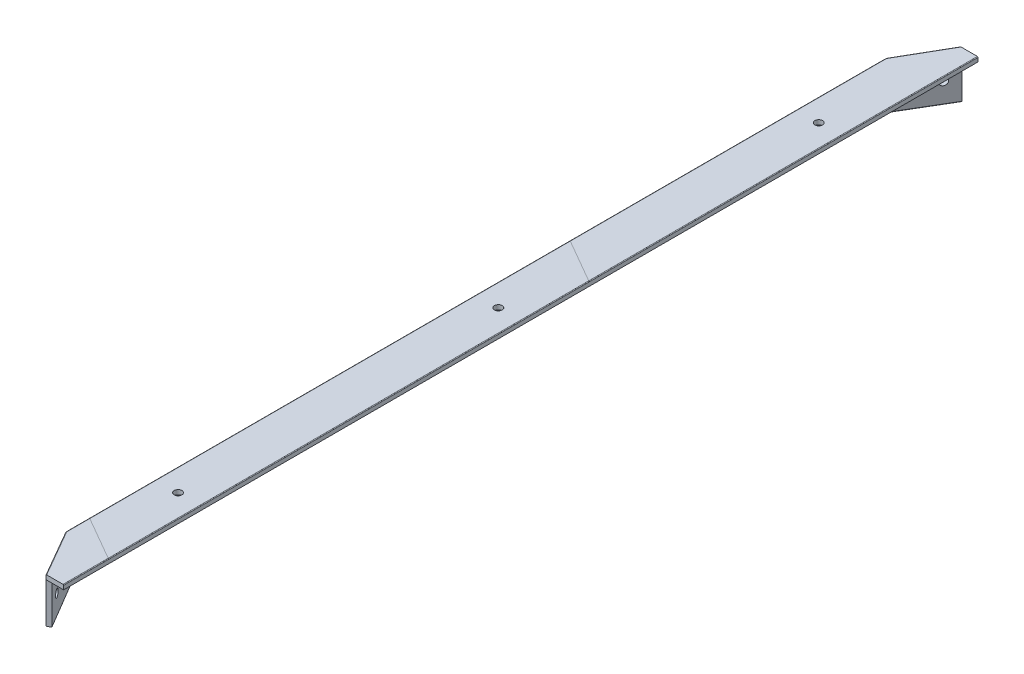
SolidWorks part; units mm, degrees
material "1.0116 (S235J2G3)"
ref_plane "Front Plane" through (0, 0, 0) normal (0, 0, 1) x (1, 0, 0)
ref_plane "Top Plane" through (0, 0, 0) normal (0, 1, 0) x (1, 0, 0)
ref_plane "Right Plane" through (0, 0, 0) normal (1, 0, 0) x (0, 0, -1)
sketch "Sketch1" plane through (0, 0, 0) normal (0, 0, 1) x (1, 0, 0)
  line L6 (0, 0) -> (0, 70)
  line L7 (0, 70) -> (70, 70)
  line L8 (70, 70) -> (70, 63)
  line L9 (70, 63) -> (7, 63)
  line L10 (7, 63) -> (7, 0)
  line L11 (7, 0) -> (0, 0)
  dimension "D1" = 70
  dimension "D2" = 70
  dimension "D3" = 7
  dimension "D4" = 7
extrude "Boss-Extrude1" add sketch "Sketch1" along normal blind 640
sketch "Sketch21" plane through (0, 0, 0) normal (0, 0, -1) x (-1, 0, 0)
  line L0 (0, 70) -> (-70, 70) construction
  line L1 (-70, 70) -> (-70, 0) construction
  line L2 (-70, 0) -> (0, 0) construction
  line L3 (0, 0) -> (0, 69.2595) construction
sketch "Sketch22" plane through (0, 70, 0) normal (0, 1, 0) x (1, 0, 0)
  line L0 (70, 0) -> (0, 0) construction
  line L1 (0, -55) -> (0, 55) construction
  circle A0 centre (35, 0) radius 6
  circle A1 centre (35, 500) radius 6
  circle A2 centre (35, -500) radius 6
  dimension "D1" = 12
  dimension "D2" = 12
  dimension "D3" = 12
  dimension "D4" = 500
  dimension "D5" = 500
  dimension "D6" = 35
  dimension "D7" = 35
extrude "Cut-Extrude4" cut sketch "Sketch22" against normal blind 10
sketch "Sketch23" plane through (0, 0, 0) normal (0, 1, 0) x (1, 0, 0)
  line L0 (0, -640) -> (42.5, -713.6122)
  line L1 (42.5, -713.6122) -> (48.5622, -710.1122)
  line L2 (48.5622, -710.1122) -> (7, -640)
  line L3 (7, -640) -> (0, -640)
  line L4 (0, -55) -> (0, 55) construction
  dimension "D1" = 7
  dimension "D2" = 210
  dimension "D3" = 85
extrude "Boss-Extrude2" add sketch "Sketch23" along normal blind 63
sketch "Sketch25" plane through (0, 63, 0) normal (0, 1, 0) x (1, 0, 0)
  line L0 (70, -640) -> (0, -640)
  line L1 (70, -640) -> (70, 0) construction
  line L2 (7, -640) -> (70, -640) construction
  line L3 (0, -640) -> (42.5, -713.6122) construction
  line L4 (0, -640) -> (42.5, -713.6122)
  line L5 (42.5, -713.6122) -> (48.5622, -710.1122) construction
  line L6 (42.5, -713.6122) -> (70, -713.6122)
  line L7 (70, -713.6122) -> (70, -640)
extrude "Boss-Extrude3" add sketch "Sketch25" along normal blind 7
sketch "Sketch26" plane through (-275.5567, 0, 163.3488) normal (0.8602, 0, -0.5099) x (-0.5099, 0, -0.8602)
  line L0 (-635.6125, 0) -> (-554.1071, 0) construction
  line L1 (-635.6125, 63) -> (-635.6125, 0) construction
  line L2 (-554.1071, 0) -> (-554.1071, 63) construction
  circle A0 centre (-614.3625, 31.5) radius 6
  circle A1 centre (-575.3671, 31.5) radius 6
  dimension "D1" = 12
  dimension "D2" = 12
  dimension "D3" = 31.5
  dimension "D4" = 31.5
  dimension "D5" = 21.25
  dimension "D6" = 21.26
extrude "Cut-Extrude5" cut sketch "Sketch26" against normal blind 7
mirror "Mirror1" about plane through (0, 0, 0) normal (0, 0, 1) of bodies 114 116
fillet "Fillet1" radius 10 2 edges at (0, 35, -640) (0, 35, 640)
fillet "Fillet2" radius 10 2 edges at (7, 31.5, 640) (7, 31.5, -640)
sketch "Sketch27" plane through (0, 70, 0) normal (0, 1, 0) x (1, 0, 0)
  line L0 (0, -603.1976) -> (70, -643.6122)
  line L1 (0, -38.5) -> (0, 38.5) construction
  line L2 (70, -713.6122) -> (70, 713.6122) construction
  line L3 (70, -643.6122) -> (70, 106.3878)
  line L4 (70, 106.3878) -> (0, 146.8024)
  line L5 (0, 146.8024) -> (0, -603.1976)
  line L6 (42.5, -713.6122) -> (70, -713.6122) construction
  dimension "D1" = 60
  dimension "D2" = 60
  dimension "D3" = 70
  dimension "D4" = 750
split line "Split Line1"
fillet "Fillet3" radius 5 5 edges at (28.48, 63, 676.2351) (7.3558, 63, 639.9025) (28.48, 63, -676.2351) (7.3558, 63, -639.9025) (7, 63, 0)
fillet "Fillet5" radius 1 20 edges at (21.9199, 0, 677.9663) (0.3407, 0, 639.9087) (21.9199, 0, -677.9663) (0.3407, 0, -639.9087) (28.48, 0, 676.2351) (7.3558, 0, 639.9025) (28.48, 0, -676.2351) (7.3558, 0, -639.9025) (70, 70, 678.6122) (70, 70, -410) (70, 70, 268.6122) (21.9199, 70, 677.9663) (0.3407, 70, 639.9087) (0, 70, 620.2591) (0, 70, 228.1976) (0, 70, -392.0614) (21.9199, 70, -677.9663) (0.3407, 70, -639.9087) (0, 0, 0) (7, 0, 0)
